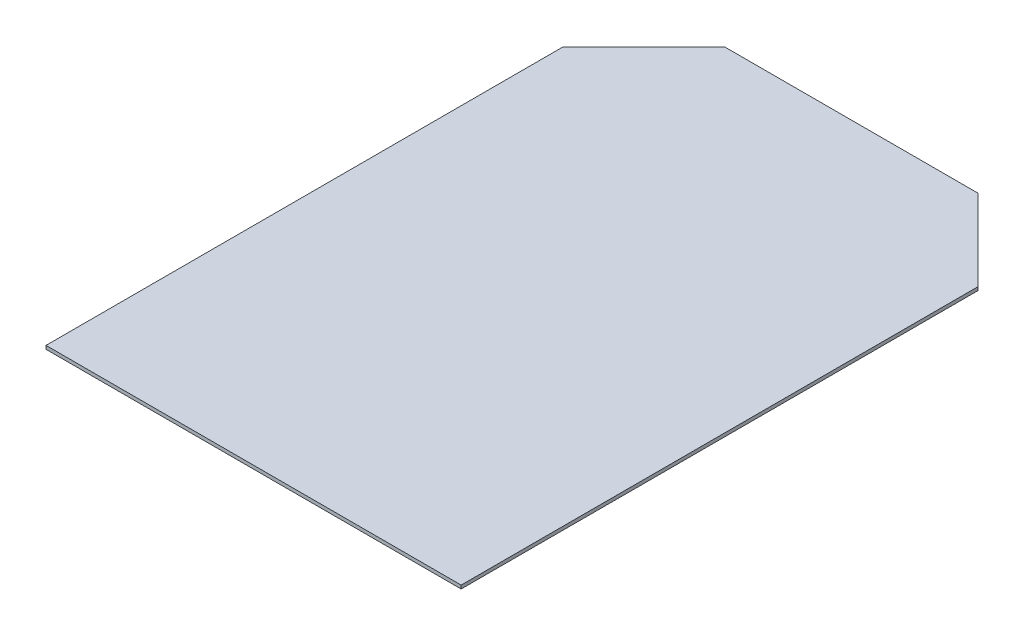
SolidWorks part; units mm, degrees
ref_plane "Front Plane" through (0, 0, 0) normal (0, 0, 1) x (1, 0, 0)
ref_plane "Top Plane" through (0, 0, 0) normal (0, 1, 0) x (1, 0, 0)
ref_plane "Right Plane" through (0, 0, 0) normal (1, 0, 0) x (0, 0, -1)
sketch "BaseSketch" plane through (0, 0, 0) normal (0, 1, 0) x (1, 0, 0)
  line L0 (134.62, 317.5) -> (215.9, 236.22) construction
  line L1 (-139.7, -317.5) -> (139.7, -317.5)
  line L2 (-215.9, -190.5) -> (-215.9, 317.5)
  line L3 (-215.9, 317.5) -> (215.9, 317.5)
  line L4 (215.9, -190.5) -> (215.9, 317.5)
  line L5 (-215.9, -317.5) -> (215.9, 317.5) construction
  line L6 (-215.9, 317.5) -> (215.9, -317.5) construction
  line L7 (215.9, -190.5) -> (139.7, -190.5)
  line L8 (139.7, -190.5) -> (139.7, -317.5)
  line L9 (139.7, -317.5) -> (-139.7, -317.5)
  line L10 (-139.7, -317.5) -> (-139.7, -190.5)
  line L11 (-139.7, -190.5) -> (-215.9, -190.5)
  line L12 (215.9, -190.5) -> (215.9, -317.5) construction
  line L13 (215.9, -317.5) -> (139.7, -317.5) construction
  line L14 (-139.7, -317.5) -> (-215.9, -317.5) construction
  line L15 (-215.9, -317.5) -> (-215.9, -190.5) construction
  line L16 (-215.9, 236.22) -> (-134.62, 317.5) construction
  line L17 (0, -2.0955) -> (0, 2.0955) construction
  point P0 (0, 0)
  dimension "D1" = 90
extrude "Boss-Extrude1" add sketch "BaseSketch" along normal blind 3.81 contours L11 L10 L1 L8 L7 L4 L3 L2 region at (0, 0, -19.2911)
sketch "Sketch7" plane through (0, 3.81, 0) normal (0, 1, 0) x (1, 0, 0)
  line L1 (-215.9, 317.5) -> (215.9, 317.5) construction
  line L2 (-215.9, -190.5) -> (-215.9, 317.5) construction
  line L3 (-139.7, -317.5) -> (139.7, -317.5) construction
  line L4 (215.9, -190.5) -> (215.9, 317.5) construction
  line L12 (230.9, -332.5) -> (230.9, 332.5)
  line L13 (230.9, 332.5) -> (-230.9, 332.5)
  line L14 (-230.9, 332.5) -> (-230.9, -332.5)
  line L15 (-230.9, -332.5) -> (230.9, -332.5)
  dimension "D1" = 15
  dimension "D2" = 15
  dimension "D3" = 15
  dimension "D4" = 15
extrude "Boss-Extrude2" add sketch "Sketch7" against normal up to surface (3.81 mm away) up to face at (0, 0, 95.25)
sketch "Sketch8" plane through (0, 3.81, 0) normal (0, 1, 0) x (1, 0, 0)
  line L0 (-230.9, 332.5) -> (-230.9, 242.4332)
  line L1 (-230.9, 332.5) -> (-230.9, -332.5) construction
  line L2 (-230.9, 242.4332) -> (-140.8332, 332.5)
  line L3 (230.9, 332.5) -> (-230.9, 332.5) construction
  line L4 (-140.8332, 332.5) -> (-230.9, 332.5)
  line L5 (140.8332, 332.5) -> (230.9, 242.4332)
  line L6 (230.9, -332.5) -> (230.9, 332.5) construction
  line L7 (230.9, 242.4332) -> (230.9, 332.5)
  line L8 (230.9, 332.5) -> (140.8332, 332.5)
  line L9 (-215.9, 236.22) -> (-134.62, 317.5) construction
  line L10 (134.62, 317.5) -> (215.9, 236.22) construction
  dimension "D1" = 15
  dimension "D2" = 15
extrude "Cut-Extrude1" cut sketch "Sketch8" against normal through all
